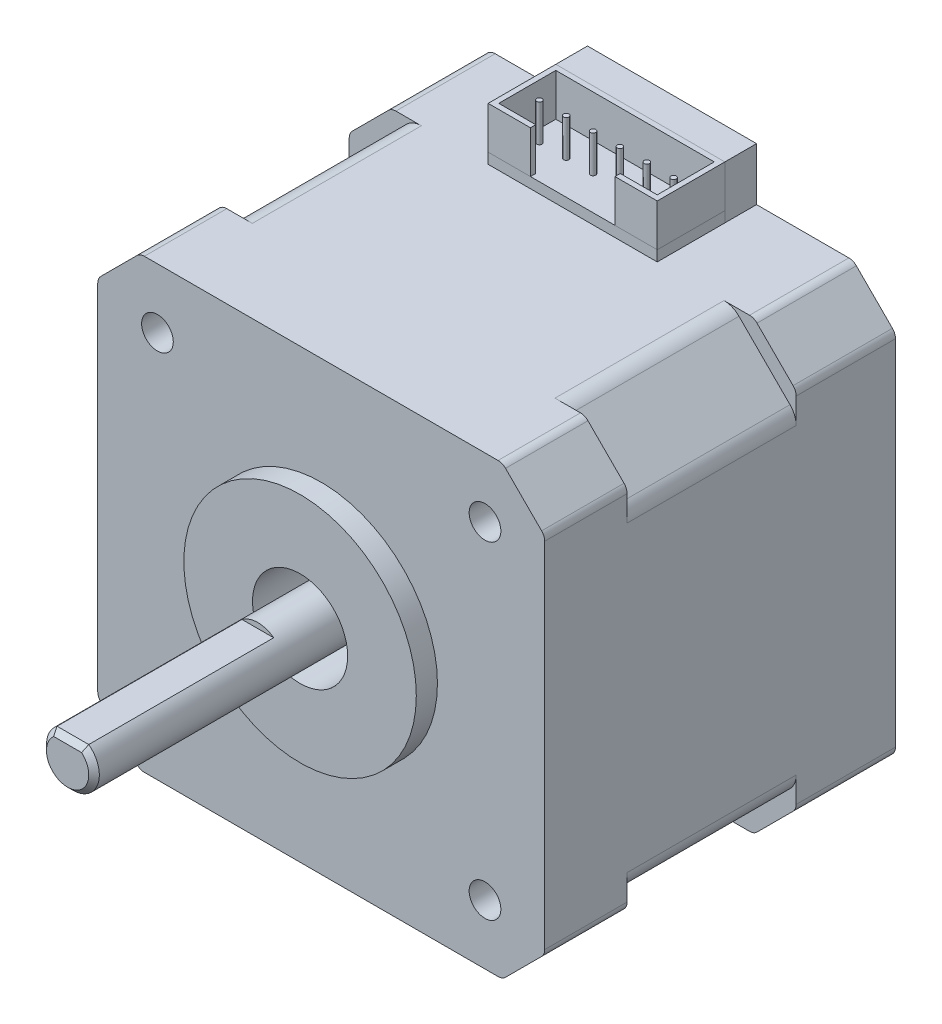
SolidWorks part; units mm, degrees
ref_plane "前视基准面" through (0, 0, 0) normal (0, 0, 1) x (1, 0, 0)
ref_plane "上视基准面" through (0, 0, 0) normal (0, 1, 0) x (1, 0, 0)
ref_plane "右视基准面" through (0, 0, 0) normal (1, 0, 0) x (0, 0, -1)
sketch "草图1" plane through (0, 0, 0) normal (0, 0, 1) x (1, 0, 0)
  line L0 (0.2929, 38.5929) -> (3.7071, 42.0071)
  line L1 (4.4142, 0) -> (37.8858, 0)
  line L2 (0, 4.4142) -> (0, 37.8858)
  line L3 (4.4142, 42.3) -> (37.8858, 42.3)
  line L4 (42.3, 4.4142) -> (42.3, 37.8858)
  line L5 (38.5929, 42.0071) -> (42.0071, 38.5929)
  line L6 (38.5929, 0.2929) -> (42.0071, 3.7071)
  line L7 (3.7071, 0.2929) -> (0.2929, 3.7071)
  arc A0 (3.7071, 0.2929) -> (4.4142, 0) centre (4.4142, 1) ccw
  arc A1 (0.2929, 3.7071) -> (0, 4.4142) centre (1, 4.4142) cw
  arc A2 (38.5929, 0.2929) -> (37.8858, 0) centre (37.8858, 1) cw
  arc A3 (42.0071, 3.7071) -> (42.3, 4.4142) centre (41.3, 4.4142) ccw
  arc A4 (42.0071, 38.5929) -> (42.3, 37.8858) centre (41.3, 37.8858) cw
  arc A5 (37.8858, 42.3) -> (38.5929, 42.0071) centre (37.8858, 41.3) cw
  arc A6 (0, 37.8858) -> (0.2929, 38.5929) centre (1, 37.8858) cw
  arc A7 (3.7071, 42.0071) -> (4.4142, 42.3) centre (4.4142, 41.3) cw
  point P1 (0, 0)
  point P2 (42.3, 42.3)
  point P3 (0, 42.3)
  point P4 (42.3, 0)
  point P15 (4, 0)
  point P18 (0, 4)
  point P21 (38.3, 0)
  point P24 (42.3, 4)
  point P27 (42.3, 38.3)
  point P30 (38.3, 42.3)
  point P33 (0, 38.3)
  point P36 (4, 42.3)
  dimension "D2" = 1
  dimension "D1" = 42.3
extrude "凸台-拉伸1" add sketch "草图1" along normal blind 33.2
ref_plane "基准面1" through (0, 0, 25.4) normal (0, 0, 1) x (1, 0, 0)
sketch "草图3" plane through (0, 0, 25.4) normal (0, 0, 1) x (1, 0, 0)
  line L8 (5.4142, 41.7142) -> (0.5858, 36.8858)
  line L9 (0.5858, 5.4142) -> (5.4142, 0.5858)
  line L10 (36.8858, 0.5858) -> (41.7142, 5.4142)
  line L11 (41.7142, 36.8858) -> (36.8858, 41.7142)
  line L12 (42.3, 6.8284) -> (42.3, 0)
  line L13 (0, 42.3) -> (6.8284, 42.3)
  line L14 (0, 42.3) -> (0, 35.4716)
  line L15 (0, 0) -> (6.8284, 0)
  line L16 (42.3, 42.3) -> (42.3, 35.4716)
  line L17 (35.4716, 0) -> (42.3, 0)
  line L18 (0, 6.8284) -> (0, 0)
  line L19 (35.4716, 42.3) -> (42.3, 42.3)
  arc A0 (35.4716, 42.3) -> (36.8858, 41.7142) centre (35.4716, 40.3) cw
  arc A1 (41.7142, 36.8858) -> (42.3, 35.4716) centre (40.3, 35.4716) cw
  arc A2 (42.3, 6.8284) -> (41.7142, 5.4142) centre (40.3, 6.8284) cw
  arc A3 (36.8858, 0.5858) -> (35.4716, 0) centre (35.4716, 2) cw
  arc A4 (5.4142, 0.5858) -> (6.8284, 0) centre (6.8284, 2) ccw
  arc A5 (0, 6.8284) -> (0.5858, 5.4142) centre (2, 6.8284) ccw
  arc A6 (0.5858, 36.8858) -> (0, 35.4716) centre (2, 35.4716) ccw
  arc A7 (5.4142, 41.7142) -> (6.8284, 42.3) centre (6.8284, 40.3) cw
  point P0 (0, 0)
  point P1 (42.3, 0)
  point P3 (42.3, 42.3)
  point P4 (0, 42.3)
  point P34 (36.3, 42.3)
  point P37 (42.3, 36.3)
  point P40 (42.3, 6)
  point P43 (36.3, 0)
  point P46 (6, 0)
  point P49 (0, 6)
  point P52 (0, 36.3)
  point P55 (6, 42.3)
  dimension "D2" = 2
extrude "切除-拉伸1" cut sketch "草图3" against normal blind 16
sketch "草图4" plane through (0, 0, 0) normal (0, 0, -1) x (-1, 0, 0)
  line L0 (-37.8858, 42.3) -> (-4.4142, 42.3) construction
  line L1 (-29.15, 42.3) -> (-13.15, 42.3)
  line L2 (-29.15, 42.3) -> (-29.15, 47.3)
  line L3 (-29.15, 47.3) -> (-13.15, 47.3)
  line L4 (-13.15, 42.3) -> (-13.15, 47.3)
  line L5 (-21.15, 50.1254) -> (-21.15, 39.617) construction
  line L6 (0, 37.8858) -> (0, 4.4142) construction
  line L7 (-42.3, 4.4142) -> (-42.3, 37.8858) construction
  point P13 (-21.15, 47.3)
  dimension "D1" = 5
  dimension "D2" = 16
extrude "凸台-拉伸2" add sketch "草图4" against normal blind 3
sketch "草图5" plane through (0, 0, 0) normal (0, 0, -1) x (-1, 0, 0)
  line L0 (-21.15, 45.5609) -> (-21.15, -5.421) construction
  line L1 (-60.9132, 21.15) -> (18.6132, 21.15) construction
  line L2 (0, 37.8858) -> (0, 4.4142) construction
  line L3 (-42.3, 4.4142) -> (-42.3, 37.8858) construction
  line L4 (-4.4142, 0) -> (-37.8858, 0) construction
  line L5 (-13.15, 42.3) -> (-4.4142, 42.3) construction
  circle A0 centre (-36.65, 36.65) radius 1.5
  circle A1 centre (-5.65, 36.65) radius 1.5
  circle A2 centre (-5.65, 5.65) radius 1.5
  circle A3 centre (-36.65, 5.65) radius 1.5
  circle A4 centre (-21.15, 21.15) radius 4.5
  point P6 (-21.15, 21.15)
  point P16 (-21.15, 21.15)
  dimension "D1" = 3
  dimension "D3" = 9
  dimension "D2" = 31
  dimension "D4" = 4
extrude "切除-拉伸2" cut sketch "草图5" against normal blind 4.5
sketch "草图6" plane through (0, 0, 4.5) normal (0, 0, -1) x (-1, 0, 0)
  line L1 (-4.4142, 0) -> (-37.8858, 0) construction
  circle A0 centre (-21.15, 21.15) radius 2.2
  dimension "D1" = 4.4
extrude "凸台-拉伸3" add sketch "草图6" along normal blind 2
sketch "草图7" plane through (0, 0, 0) normal (0, 0, -1) x (-1, 0, 0)
  circle A0 centre (-36.65, 36.65) radius 3
  circle A1 centre (-5.5972, 36.5006) radius 3
  circle A2 centre (-5.7465, 5.4478) radius 3
  circle A3 centre (-36.7994, 5.5972) radius 3
  point P12 (-21.1983, 21.0489)
  dimension "D1" = 6
extrude "切除-拉伸3" cut sketch "草图7" against normal blind 2
sketch "草图8" plane through (0, 0, 33.2) normal (0, 0, 1) x (1, 0, 0)
  circle A0 centre (5.65, 5.65) radius 1.5 construction
  circle A1 centre (36.65, 5.65) radius 1.5 construction
  circle A2 centre (36.65, 36.65) radius 1.5 construction
  circle A3 centre (5.65, 36.65) radius 1.5 construction
  circle A4 centre (5.65, 5.65) radius 1.5
  circle A5 centre (36.65, 5.65) radius 1.5
  circle A6 centre (36.65, 36.65) radius 1.5
  circle A7 centre (5.65, 36.65) radius 1.5
  circle A8 centre (21.15, 21.15) radius 4.5 construction
  circle A9 centre (21.15, 21.15) radius 4.5
extrude "切除-拉伸4" cut sketch "草图8" against normal blind 4.5
sketch "草图9" plane through (0, 0, 28.7) normal (0, 0, 1) x (1, 0, 0)
  circle A0 centre (21.15, 21.15) radius 2.5
  dimension "D1" = 5
extrude "凸台-拉伸4" add sketch "草图9" along normal offset from surface (28.5 mm away) 24 up to face at (25.65, 21.15, 33.2) offset beyond the face yes
sketch "草图10" plane through (0, 0, 57.2) normal (0, 0, 1) x (1, 0, 0)
  line L0 (19.65, 23.15) -> (22.65, 23.15)
  circle A0 centre (21.15, 21.15) radius 2.5 construction
  circle A2 centre (21.15, 21.15) radius 2.5
  arc A3 (22.65, 23.15) -> (19.65, 23.15) centre (21.15, 21.15) ccw
  dimension "D2" = 2
  dimension "D1" = 0
extrude "切除-拉伸5" cut sketch "草图10" against normal blind 18
chamfer "倒角1" distance 0.5 angle 45 2 edges at (21.15, 23.15, 57.2) (21.15, 18.65, 57.2)
sketch "草图11" plane through (0, 0, 33.2) normal (0, 0, 1) x (1, 0, 0)
  circle A0 centre (21.15, 21.15) radius 11
  circle A1 centre (21.15, 21.15) radius 4.5 construction
  circle A2 centre (21.15, 21.15) radius 4.5
  dimension "D1" = 22
extrude "凸台-拉伸5" add sketch "草图11" along normal blind 2
sketch "草图12" plane through (0, 0, 4.5) normal (0, 0, -1) x (-1, 0, 0)
  circle A0 centre (-21.15, 21.15) radius 3.5
  dimension "D1" = 7
extrude "凸台-拉伸6" add sketch "草图12" along normal blind 1
sketch "草图13" plane through (0, 0, 28.7) normal (0, 0, 1) x (1, 0, 0)
  circle A0 centre (21.15, 21.15) radius 3.5
  dimension "D1" = 7
extrude "凸台-拉伸7" add sketch "草图13" along normal blind 1
sketch "草图14" plane through (0, 42.3, 0) normal (0, 1, 0) x (1, 0, 0)
  line L0 (5.4142, -9.4) -> (6.8284, -9.4) construction
  line L1 (13.15, -3) -> (29.15, -3)
  line L2 (13.15, -3) -> (13.15, -9.4)
  line L3 (13.15, -9.4) -> (29.15, -9.4)
  line L4 (29.15, -3) -> (29.15, -9.4)
  line L5 (29.15, -3) -> (29.15, 0) construction
extrude "凸台-拉伸8" add sketch "草图14" along normal blind 1 separate body
sketch "草图15" plane through (0, 43.3, 0) normal (0, 1, 0) x (1, 0, 0)
  line L1 (13.15, -3) -> (13.15, -9.4) construction
  line L3 (13.15, -9.4) -> (29.15, -9.4) construction
  circle A0 centre (14.8, -6.2) radius 0.25
  circle A1 centre (17.34, -6.2) radius 0.25
  circle A2 centre (19.88, -6.2) radius 0.25
  circle A3 centre (22.42, -6.2) radius 0.25
  circle A4 centre (24.96, -6.2) radius 0.25
  circle A5 centre (27.5, -6.2) radius 0.25
  dimension "D2" = 0.5
  dimension "D3" = 1.65
  dimension "D4" = 3.2
  dimension "D1" = 6
extrude "凸台-拉伸9" add sketch "草图15" along normal offset from surface (3.5 mm away) 0.5 up to face at (21.15, 47.3, 1.5)
sketch "草图16" plane through (0, 43.3, 0) normal (0, 1, 0) x (1, 0, 0)
  line L4 (17.15, -8.9) -> (17.15, -9.4)
  line L5 (25.15, -8.9) -> (25.15, -9.4)
  line L6 (21.15, 0.9139) -> (21.15, -13.2286) construction
  line L7 (13.15, 0) -> (29.15, 0) construction
  line L8 (13.65, -3.5) -> (13.65, -8.9)
  line L9 (13.65, -8.9) -> (28.65, -8.9)
  line L10 (28.65, -8.9) -> (28.65, -3.5)
  line L11 (28.65, -3.5) -> (13.65, -3.5)
  line L12 (13.65, -3.5) -> (13.65, -8.9)
  line L13 (13.65, -8.9) -> (17.15, -8.9)
  line L14 (28.65, -8.9) -> (28.65, -3.5)
  line L16 (13.15, -3) -> (13.15, -9.4)
  line L17 (13.15, -9.4) -> (29.15, -9.4)
  line L18 (29.15, -9.4) -> (29.15, -3)
  line L19 (29.15, -3) -> (13.15, -3)
  line L20 (13.15, -3) -> (13.15, -9.4)
  line L21 (13.15, -9.4) -> (17.15, -9.4)
  line L22 (29.15, -9.4) -> (29.15, -3)
  line L24 (25.15, -9.4) -> (29.15, -9.4)
  line L25 (25.15, -8.9) -> (28.65, -8.9)
  line L30 (28.65, -3.5) -> (13.65, -3.5)
  line L31 (29.15, -3) -> (13.15, -3)
  point P16 (21.15, 0)
  dimension "D3" = 8
  dimension "D1" = 0.5
  dimension "D2" = 0
extrude "凸台-拉伸10" add sketch "草图16" along normal up to surface (4 mm away) separate body up to face at (21.15, 47.3, 1.5)
